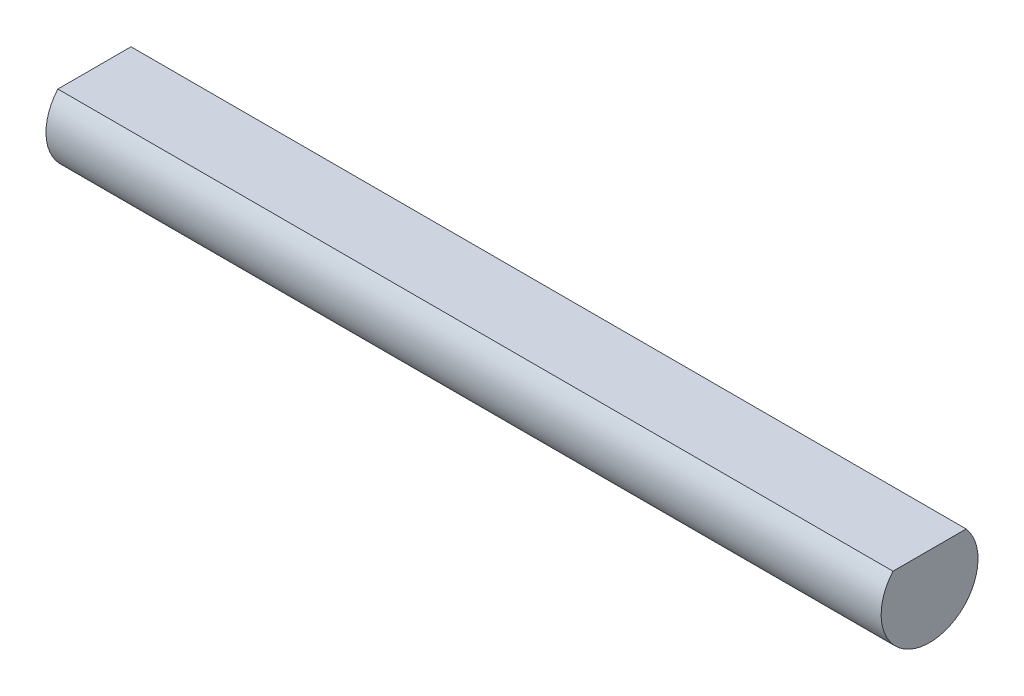
SolidWorks part; units mm, degrees
other "Markup1"
sketch "Sketch2" plane through (-12.5, 0.95, 1.45) normal (-0.2078, 0.6873, 0.696) x (0.7492, -0.3456, 0.565)
ref_plane "Front Plane" through (0, 0, 0) normal (0, 0, 1) x (1, 0, 0)
ref_plane "Top Plane" through (0, 0, 0) normal (0, 1, 0) x (1, 0, 0)
ref_plane "Right Plane" through (0, 0, 0) normal (1, 0, 0) x (0, 0, -1)
sketch "Sketch1" plane through (0, 0, 0) normal (1, 0, 0) x (0, 0, -1)
  line L0 (0, -1.5) -> (0, 1)
  line L1 (0, 1) -> (-1.118, 1)
  line L2 (-1.118, 1) -> (1.118, 1)
  line L3 (-1.0954, 0.95) -> (1.0954, 0.95)
  arc A0 (-1.118, 1) -> (1.118, 1) centre (0, 0) ccw
  arc A1 (-1.0954, 0.95) -> (1.0954, 0.95) centre (0, 0) ccw
  dimension "D1" = 3
  dimension "D2" = 2.5
  dimension "D3" = 0.05
extrude "Boss-Extrude1" add sketch "Sketch1" along normal blind 12.5 and the other way blind 12.5 contours L3 A1 L0 | L0 A1 L3 region at (0, -0.1499, 0.6405) region at (0, -0.1499, -0.6405)
